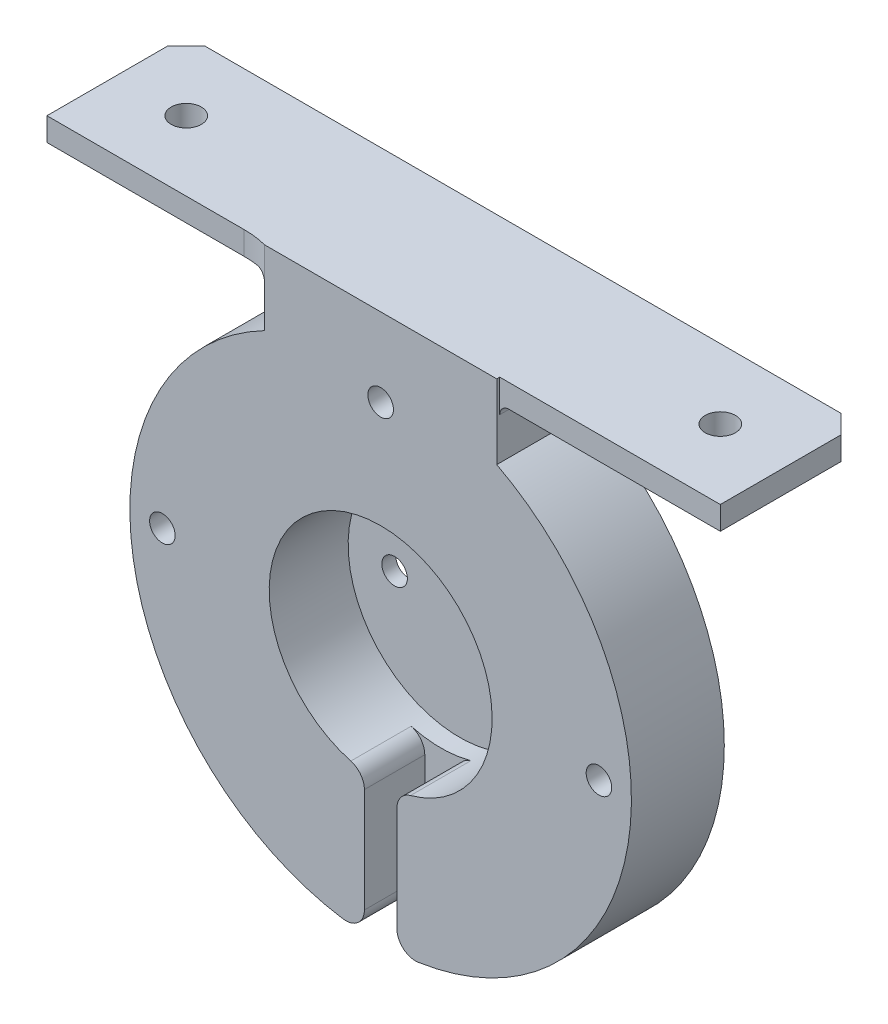
SolidWorks part; units mm, degrees
ref_plane "Front Plane" through (0, 0, 0) normal (0, 0, 1) x (1, 0, 0)
ref_plane "Top Plane" through (0, 0, 0) normal (0, 1, 0) x (1, 0, 0)
ref_plane "Right Plane" through (0, 0, 0) normal (1, 0, 0) x (0, 0, -1)
sketch "Sketch1" plane through (0, 0, 0) normal (0, 0, 1) x (1, 0, 0)
  circle A0 centre (0, 0) radius 27
  circle A1 centre (0, 0) radius 23.5 construction
  circle A2 centre (0, 23.5) radius 1.375
  circle A3 centre (23.5, 0) radius 1.375
  circle A4 centre (0, -23.5) radius 1.375 construction
  circle A5 centre (-23.5, 0) radius 1.375
  circle A6 centre (0, 0) radius 20
  point P15 (0, 0)
  dimension "D1" = 54
  dimension "D2" = 47
  dimension "D3" = 2.75
  dimension "D5" = 40
  dimension "D4" = 4
extrude "Boss-Extrude1" add sketch "Sketch1" along normal blind 10
sketch "Sketch3" plane through (0, 0, 0) normal (0, 0, 1) x (1, 0, 0)
  circle A0 centre (0, 0) radius 20
  circle A1 centre (0, 0) radius 7 construction
  circle A2 centre (-7, 0) radius 1.375
  circle A3 centre (7, 0) radius 1.375
  circle A4 centre (0, 0) radius 11.5 construction
  dimension "D1" = 40
  dimension "D2" = 14
  dimension "D3" = 2.75
  dimension "D4" = 23
extrude "Boss-Extrude2" add sketch "Sketch3" along normal blind 1.5
sketch "Sketch5" plane through (0, 0, 10) normal (0, 0, 1) x (1, 0, 0)
  line L0 (0, -5.5) -> (0, 5.5) construction
  line L1 (-12.5, 23.9322) -> (-4.2519, 23.9322)
  line L2 (-12.5, 23.9322) -> (-12.5, 31.9322)
  line L3 (-12.5, 31.9322) -> (12.5, 31.9322)
  line L4 (12.5, 23.9322) -> (12.5, 31.9322)
  line L5 (4.2678, 23.9322) -> (0, 26.2545)
  line L6 (0, 26.2545) -> (-4.2519, 23.9322)
  line L7 (4.2678, 23.9322) -> (12.5, 23.9322)
  circle A0 centre (0, 0) radius 27 construction
  dimension "D1" = 12.5
  dimension "D2" = 25
  dimension "D3" = 8
extrude "Boss-Extrude3" add sketch "Sketch5" against normal blind 6
sketch "Sketch6" plane through (0, 31.9322, 0) normal (0, 1, 0) x (1, 0, 0)
  line L0 (12.5, -4) -> (12.5, -10) construction
  line L1 (-12.5, -10) -> (12.5, -10)
  line L2 (-12.5, -10) -> (-12.5, 5.32)
  line L3 (-12.5, 5.32) -> (12.5, 5.32)
  line L4 (12.5, -10) -> (12.5, 5.32)
  dimension "D1" = 15.32
extrude "Boss-Extrude4" add sketch "Sketch6" against normal blind 2.5
sketch "Sketch7" plane through (0, 31.9322, 0) normal (0, 1, 0) x (1, 0, 0)
  line L0 (0, -5.5) -> (0, 5.5) construction
  line L1 (-36.25, -67.18) -> (36.25, -67.18) construction
  line L2 (-36.25, -67.18) -> (-36.25, 1.32) construction
  line L3 (-32.25, 5.32) -> (32.25, 5.32) construction
  line L4 (36.25, -67.18) -> (36.25, 1.32) construction
  line L5 (-28.75, -9.68) -> (-36.25, -9.68)
  line L6 (0, 5.32) -> (-36.25, 5.32)
  line L7 (-36.25, -9.68) -> (-36.25, -2.18)
  line L8 (12.5, -4) -> (-12.5, -4) construction
  line L9 (0, 5.32) -> (0, -9.68)
  line L10 (0, -9.68) -> (-28.75, -9.68)
  line L11 (-36.25, 5.32) -> (-36.25, -2.18)
  arc A0 (32.25, 5.32) -> (36.25, 1.32) centre (32.25, 1.32) cw construction
  circle A3 centre (-28.75, -2.18) radius 1.625
  point P4 (0, 5.32)
  point P11 (36.25, 5.32)
  point P14 (-36.25, 5.32)
  point P21 (-36.25, -9.68)
  dimension "D4" = 4
  dimension "D7" = 3.25
  dimension "D1" = 72.5
  dimension "D2" = 72.5
  dimension "D3" = 9.32
  dimension "D5" = 15
extrude "Boss-Extrude5" add sketch "Sketch7" against normal blind 2.5 contours L10 L9 L6 L11 A3 region at (-17.9604, 31.9322, 2.18)
fillet "Fillet2" radius 10 1 edges at (-12.5, 30.6822, 9.68)
sketch "Sketch8" plane through (0, 31.9322, 0) normal (0, 1, 0) x (1, 0, 0)
  circle A0 centre (-28.75, -2.18) radius 2.5
  circle A1 centre (-28.75, -2.18) radius 4
  dimension "D1" = 5
  dimension "D2" = 8
extrude "Boss-Extrude6" [suppressed] add sketch "Sketch8" against normal blind 5
mirror "Mirror1" about plane through (0, 0, 0) normal (1, 0, 0) of "Boss-Extrude4", "Boss-Extrude5", "Boss-Extrude6"
fillet "Fillet3" radius 1 3 edges at (0, 29.4322, 4) (12.5, 29.4322, 6.84) (-12.5, 29.4322, 7)
fillet "Fillet4" [suppressed] radius 10
chamfer "Chamfer1" distance 2 angle 45 2 edges at (-36.25, 30.6822, -5.32) (36.25, 30.6822, -5.32)
sketch "Sketch9" plane through (0, 0, 1.5) normal (0, 0, 1) x (1, 0, 0)
  circle A0 centre (0, 0) radius 12
  circle A1 centre (0, 0) radius 20
  dimension "D1" = 24
extrude "Boss-Extrude7" add sketch "Sketch9" along normal up to surface (8.5 mm away) up to face at (-2.5, 17.8458, 10)
sketch "Sketch4" plane through (0, 0, 0) normal (0, 1, 0) x (1, 0, 0)
  line L0 (12.5, -10) -> (-12.5, -10) construction
  line L1 (-1.75, -3.5) -> (1.75, -3.5)
  line L2 (-1.75, -3.5) -> (-1.75, -10)
  line L3 (-1.75, -10) -> (1.75, -10)
  line L4 (1.75, -3.5) -> (1.75, -10)
  line L5 (-29.7, 0) -> (29.7, 0) construction
  point P6 (1.4897, -13.5903)
  point P7 (0, -3.5)
  point P8 (-1.75, -10)
  dimension "D1" = 3.5
  dimension "D2" = 3.5
extrude "Cut-Extrude1" cut sketch "Sketch4" against normal up to surface (26.9432 mm away) up to face at (0, 11.9661, 7)
fillet "Fillet6" radius 2 4 edges at (1.75, -11.8717, 6.75) (-1.75, -11.8717, 6.75) (1.75, -26.9432, 6.75) (-1.75, -26.9432, 6.75)
sketch "Sketch10" plane through (0, 0, 10) normal (0, 0, 1) x (1, 0, 0)
  line L0 (-4.25, -19.5432) -> (-4.25, -13.8632)
  line L1 (-1.75, -24.7171) -> (-1.75, -13.4884) construction
  line L2 (0, -8.4586) -> (0, 8.4586) construction
  line L3 (4.25, -19.5432) -> (4.25, -13.8632)
  arc A0 (4.25, -19.5432) -> (-4.25, -19.5432) centre (0, 0) ccw
  arc A1 (-12.5, 23.9322) -> (-4.05, -26.6945) centre (0, 0) ccw construction
  arc A2 (4.25, -13.8632) -> (-4.25, -13.8632) centre (0, 0) ccw
  circle A3 centre (0, 0) radius 12 construction
  dimension "D1" = 7
  dimension "D2" = 2.5
  dimension "D3" = 2.5
extrude "Cut-Extrude2" [suppressed] cut sketch "Sketch10" against normal up to surface (6.5 mm away) up to face at (0, -19.2787, 3.5)
